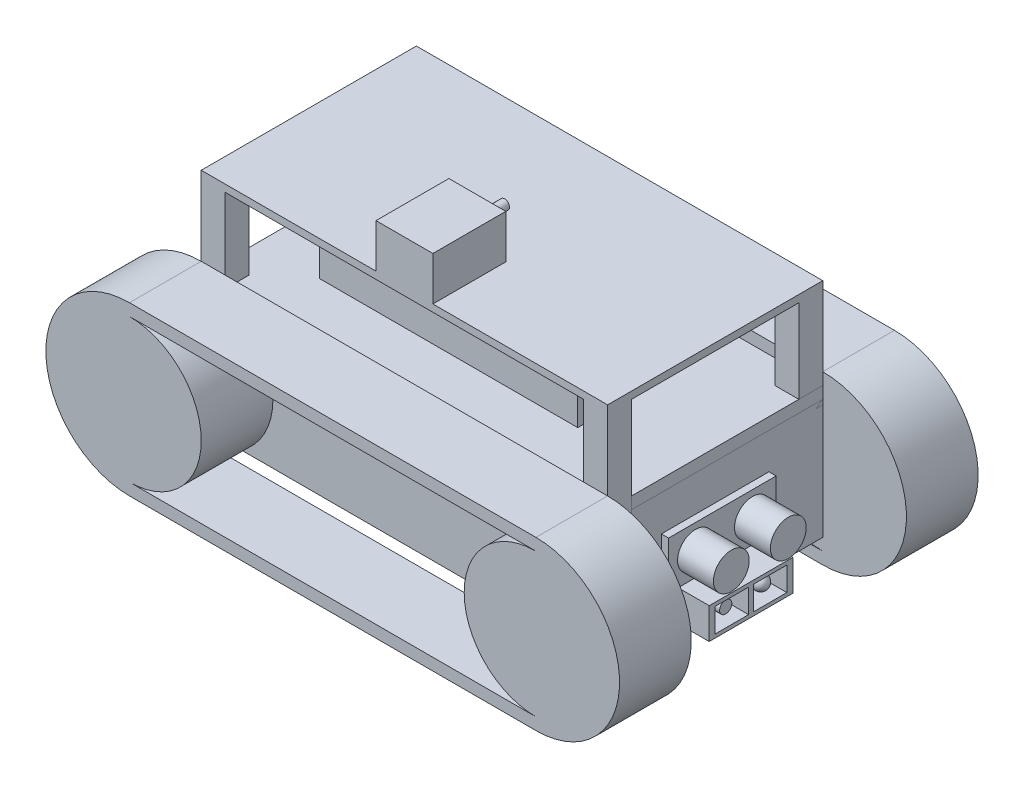
SolidWorks part; units mm, degrees
ref_plane "Front Plane" through (0, 0, 0) normal (0, 0, 1) x (1, 0, 0)
ref_plane "Top Plane" through (0, 0, 0) normal (0, 1, 0) x (1, 0, 0)
ref_plane "Right Plane" through (0, 0, 0) normal (1, 0, 0) x (0, 0, -1)
sketch "Sketch1" plane through (0, 0, 0) normal (0, 1, 0) x (1, 0, 0)
  line L1 (0, 0) -> (170, 0)
  line L2 (0, 0) -> (0, 90)
  line L3 (0, 90) -> (170, 90)
  line L4 (170, 0) -> (170, 90)
  dimension "D1" = 170
  dimension "D2" = 90
extrude "Boss-Extrude1" add sketch "Sketch1" along normal blind 50 contours L3 L4 L1 L2
sketch "Sketch2" plane through (0, 0, 0) normal (0, 0, 1) x (1, 0, 0)
  line L0 (170, 50) -> (170, 0) construction
  line L1 (0, 50) -> (0, 0) construction
  circle A0 centre (170, 25) radius 30
  circle A1 centre (0, 25) radius 30
  dimension "D1" = 60
  dimension "D2" = 60
extrude "Boss-Extrude2" add sketch "Sketch2" along normal blind 30
pattern_linear "LPattern1" count 2 spacing 120 along (0, 0, -1) of "Boss-Extrude2"
sketch "Sketch3" plane through (0, 0, 30) normal (0, 0, 1) x (1, 0, 0)
  line L0 (0, 60) -> (170, 60)
  line L1 (0, -10) -> (170, -10)
  line L2 (170, 55) -> (0, 55)
  line L3 (0, -5) -> (170, -5)
  circle A0 centre (170, 25) radius 35 construction
  circle A1 centre (0, 25) radius 35 construction
  circle A2 centre (0, 25) radius 30 construction
  circle A3 centre (170, 25) radius 30 construction
  arc A4 (170, 60) -> (170, -10) centre (170, 25) cw
  arc A5 (170, 55) -> (170, -5) centre (170, 25) cw
  arc A6 (0, 60) -> (0, -10) centre (0, 25) ccw
  arc A7 (0, -5) -> (0, 55) centre (0, 25) cw
  dimension "D1" = 70
  dimension "D2" = 70
extrude "Boss-Extrude3" add sketch "Sketch3" against normal blind 30
pattern_linear "LPattern2" count 2 spacing 120 along (0, 0, -1) of "Boss-Extrude3"
sketch "Sketch4" plane through (0, 50, 0) normal (0, 1, 0) x (1, 0, 0)
  line L1 (0, 90) -> (170, 90)
  line L2 (0, 90) -> (0, 0)
  line L3 (0, 0) -> (170, 0)
  line L4 (170, 90) -> (170, 0)
extrude "Boss-Extrude6" add sketch "Sketch4" along normal blind 5 separate body
sketch "Sketch5" plane through (0, 55, 0) normal (0, 1, 0) x (1, 0, 0)
  line L0 (85, 90) -> (85, 0)
  line L1 (170, 90) -> (0, 90) construction
  line L2 (170, 0) -> (0, 0) construction
  line L6 (31, 18.5) -> (139, 18.5) construction
  line L7 (31, 18.5) -> (31, 71.5) construction
  line L8 (31, 71.5) -> (139, 71.5) construction
  line L9 (139, 18.5) -> (139, 71.5) construction
  line L10 (31, 18.5) -> (139, 71.5)
  line L11 (31, 71.5) -> (139, 18.5)
  point P6 (85, 45)
  dimension "D1" = 53
  dimension "D2" = 108
ref_plane "Plane1" through (0, 60, 0) normal (0, 1, 0) x (1, 0, 0)
sketch "Sketch6" plane through (0, 60, 0) normal (0, 1, 0) x (1, 0, 0)
  line L1 (31, 71.5) -> (139, 71.5)
  line L2 (31, 71.5) -> (31, 18.5)
  line L3 (31, 18.5) -> (139, 18.5)
  line L4 (139, 71.5) -> (139, 18.5)
  line L5 (31, 71.5) -> (139, 18.5) construction
  line L6 (31, 18.5) -> (139, 71.5) construction
  point P0 (85, 45)
extrude "Boss-Extrude7" add sketch "Sketch6" along normal blind 15 separate body
ref_plane "Plane2" through (0, 90, 0) normal (0, 1, 0) x (1, 0, 0)
sketch "Sketch7" plane through (0, 90, 0) normal (0, 1, 0) x (1, 0, 0)
  line L0 (170, 0) -> (170, -30) construction
  line L1 (0, 90) -> (170, 90)
  line L2 (0, 90) -> (0, 0)
  line L3 (0, 0) -> (170, 0)
  line L4 (170, 90) -> (170, 0)
  line L5 (0, 90) -> (170, 0) construction
  line L6 (0, 0) -> (170, 90) construction
  line L7 (205, 0) -> (170, 0) construction
  point P0 (85, 45)
extrude "Boss-Extrude8" add sketch "Sketch7" along normal blind 3 separate body
sketch "Sketch8" plane through (0, 0, 0) normal (0, 0, 1) x (1, 0, 0)
  line L0 (85, 93) -> (85, 111.3) construction
  line L1 (0, 93) -> (170, 93) construction
  line L3 (73.1, 111.3) -> (96.9, 111.3)
  line L4 (73.1, 111.3) -> (73.1, 93)
  line L5 (73.1, 93) -> (96.9, 93)
  line L6 (96.9, 111.3) -> (96.9, 93)
  line L7 (73.1, 111.3) -> (96.9, 93) construction
  line L8 (73.1, 93) -> (96.9, 111.3) construction
  point P4 (85, 102.15)
  dimension "D1" = 18.3
  dimension "D2" = 23.8
extrude "Boss-Extrude9" add sketch "Sketch8" against normal blind 30.5
sketch "Sketch9" plane through (0, 0, -30.5) normal (0, 0, -1) x (-1, 0, 0)
  line L0 (-85, 111.3) -> (-85, 93) construction
  line L1 (-96.9, 111.3) -> (-73.1, 111.3) construction
  line L2 (-73.1, 93) -> (-96.9, 93) construction
  circle A0 centre (-85, 102.15) radius 2.0061
extrude "Boss-Extrude10" add sketch "Sketch9" along normal blind 11.45
sketch "Sketch10" plane through (170, 0, 0) normal (1, 0, 0) x (0, 0, -1)
  line L0 (45, 50) -> (45, 0) construction
  line L1 (0, 50) -> (90, 50) construction
  line L2 (0, 0) -> (90, 0) construction
  line L4 (22.5, 35) -> (67.5, 35)
  line L5 (22.5, 35) -> (22.5, 15)
  line L6 (22.5, 15) -> (67.5, 15)
  line L7 (67.5, 35) -> (67.5, 15)
  line L8 (22.5, 35) -> (67.5, 15) construction
  line L9 (22.5, 15) -> (67.5, 35) construction
  point P6 (45, 25)
  dimension "D1" = 20
  dimension "D2" = 45
extrude "Boss-Extrude11" add sketch "Sketch10" along normal blind 3
sketch "Sketch11" plane through (173, 0, 0) normal (1, 0, 0) x (0, 0, -1)
  line L0 (45, 35) -> (45, 15) construction
  line L1 (67.5, 35) -> (22.5, 35) construction
  line L2 (22.5, 15) -> (67.5, 15) construction
  line L3 (45, 25) -> (22.5, 25) construction
  line L4 (22.5, 35) -> (22.5, 15) construction
  line L5 (45, 25) -> (67.5, 25) construction
  line L6 (67.5, 15) -> (67.5, 35) construction
  circle A0 centre (57.5882, 25) radius 7.5
  circle A1 centre (33.75, 25) radius 7.5
  dimension "D1" = 15
  dimension "D2" = 15
extrude "Boss-Extrude12" add sketch "Sketch11" along normal blind 15
sketch "Sketch12" plane through (170, 0, 0) normal (1, 0, 0) x (0, 0, -1)
  line L0 (45, 15) -> (45, 0) construction
  line L1 (22.5, 15) -> (67.5, 15) construction
  line L2 (0, 0) -> (90, 0) construction
  line L3 (30, 12.5) -> (44, 12.5)
  line L4 (30, 12.5) -> (60, 12.5) construction
  line L5 (30, 12.5) -> (30, 2.5)
  line L6 (30, 2.5) -> (60, 2.5) construction
  line L7 (60, 12.5) -> (60, 2.5)
  line L8 (30, 12.5) -> (60, 2.5) construction
  line L9 (30, 2.5) -> (60, 12.5) construction
  line L10 (27.5, 14) -> (62.5, 14)
  line L11 (27.5, 14) -> (27.5, 1)
  line L12 (27.5, 1) -> (62.5, 1)
  line L13 (62.5, 14) -> (62.5, 1)
  line L14 (27.5, 14) -> (62.5, 1) construction
  line L15 (27.5, 1) -> (62.5, 14) construction
  line L16 (44, 12.5) -> (46, 12.5) construction
  line L17 (44, 12.5) -> (44, 2.5)
  line L18 (44, 2.5) -> (46, 2.5) construction
  line L19 (46, 12.5) -> (46, 2.5)
  line L20 (44, 12.5) -> (46, 2.5) construction
  line L21 (44, 2.5) -> (46, 12.5) construction
  line L22 (60, 12.5) -> (46, 12.5)
  line L23 (46, 2.5) -> (60, 2.5)
  line L24 (30, 2.5) -> (44, 2.5)
  point P6 (45, 7.5)
  point P11 (45, 7.5)
  point P16 (45, 7.5)
  dimension "D1" = 30
  dimension "D2" = 10
  dimension "D3" = 35
  dimension "D4" = 13
  dimension "D5" = 2
extrude "Boss-Extrude13" add sketch "Sketch12" along normal blind 15
ref_plane "Plane3" through (180, 0, 0) normal (1, 0, 0) x (0, 0, -1)
sketch "Sketch13" plane through (180, 0, 0) normal (1, 0, 0) x (0, 0, -1)
  line L0 (37, 12.5) -> (37, 2.5) construction
  line L1 (44, 12.5) -> (30, 12.5) construction
  line L2 (30, 2.5) -> (44, 2.5) construction
  circle A0 centre (37, 7.5) radius 2.55
  dimension "D1" = 5.1
extrude "Boss-Extrude14" add sketch "Sketch13" along normal blind 2.4 separate body
ref_plane "Plane4" through (175.4, 0, 0) normal (1, 0, 0) x (0, 0, -1)
sketch "Sketch14" plane through (175.4, 0, 0) normal (1, 0, 0) x (0, 0, -1)
  line L0 (53, 12.5) -> (53, 2.5) construction
  line L1 (60, 12.5) -> (46, 12.5) construction
  line L2 (46, 2.5) -> (60, 2.5) construction
  circle A0 centre (53, 7.8643) radius 3
  dimension "D1" = 6
extrude "Boss-Extrude15" add sketch "Sketch14" along normal blind 8.6 separate body contours A0
fillet "Fillet1" radius 3 1 edges at (184, 7.8643, -56)
sketch "Sketch15" plane through (0, 0, 0) normal (-1, 0, 0) x (0, 0, 1)
  line L0 (-45, 0) -> (-45, 15) construction
  line L1 (0, 0) -> (-90, 0) construction
  line L3 (-62.5, 15) -> (-27.5, 15)
  line L4 (-62.5, 15) -> (-62.5, 0)
  line L5 (-62.5, 0) -> (-27.5, 0)
  line L6 (-27.5, 15) -> (-27.5, 0)
  line L7 (-62.5, 15) -> (-27.5, 0) construction
  line L8 (-62.5, 0) -> (-27.5, 15) construction
  point P4 (-45, 7.5)
  dimension "D1" = 15
  dimension "D2" = 35
extrude "Boss-Extrude16" add sketch "Sketch15" along normal blind 13
sketch "Sketch17" plane through (0, 0, 0) normal (0, -1, 0) x (1, 0, 0)
  line L0 (0, -62.5) -> (0, -90) construction
  line L1 (-13, -27.5) -> (0, -27.5) construction
  line L2 (-13, -27.5) -> (-13, -62.5) construction
  line L3 (-13, -62.5) -> (0, -62.5) construction
  line L4 (0, -27.5) -> (0, -62.5) construction
  line L5 (0, -45) -> (-13, -45) construction
  line L7 (-11.5, -60) -> (-1.5, -60)
  line L8 (-11.5, -60) -> (-11.5, -30)
  line L9 (-11.5, -30) -> (-1.5, -30)
  line L10 (-1.5, -60) -> (-1.5, -30)
  line L11 (-11.5, -60) -> (-1.5, -30) construction
  line L12 (-11.5, -30) -> (-1.5, -60) construction
  point P9 (-6.5, -45)
  dimension "D1" = 30
  dimension "D2" = 10
extrude "Cut-Extrude1" cut sketch "Sketch17" against normal blind 12 contours L8 L9 L10 L7
sketch "Sketch18" plane through (0, 12, 0) normal (0, -1, 0) x (1, 0, 0)
  line L0 (-11.5, -44.4175) -> (-1.5, -44.4175) construction
  line L1 (-11.5, -60) -> (-11.5, -30) construction
  line L2 (-1.5, -60) -> (-1.5, -30) construction
  line L4 (-11.5, -43.4175) -> (-1.5, -43.4175)
  line L5 (-11.5, -43.4175) -> (-11.5, -45.4175)
  line L6 (-11.5, -45.4175) -> (-1.5, -45.4175)
  line L7 (-1.5, -43.4175) -> (-1.5, -45.4175)
  line L8 (-11.5, -43.4175) -> (-1.5, -45.4175) construction
  line L9 (-11.5, -45.4175) -> (-1.5, -43.4175) construction
  point P6 (-6.5, -44.4175)
  dimension "D1" = 2
extrude "Boss-Extrude17" add sketch "Sketch18" along normal blind 12
sketch "Sketch20" plane through (0, 90, 0) normal (0, -1, 0) x (1, 0, 0)
  line L1 (0, 0) -> (10, 0)
  line L2 (0, 0) -> (0, -10)
  line L3 (0, -10) -> (10, -10)
  line L4 (10, 0) -> (10, -10)
  line L5 (170, 0) -> (170, -90) construction
  line L6 (170, 0) -> (160, 0)
  line L7 (170, 0) -> (170, -10)
  line L8 (170, -10) -> (160, -10)
  line L11 (160, 0) -> (160, -10)
  line L12 (0, 0) -> (170, 0) construction
  line L13 (170, -90) -> (0, -90) construction
  line L14 (170, -90) -> (160, -90)
  line L16 (170, -90) -> (170, -80)
  line L17 (170, -80) -> (160, -80)
  line L18 (160, -90) -> (160, -80)
  line L19 (0, -90) -> (0, 0) construction
  line L20 (0, -90) -> (10, -90)
  line L21 (0, -90) -> (0, -80)
  line L22 (0, -80) -> (10, -80)
  line L23 (10, -90) -> (10, -80)
  dimension "D1" = 10
  dimension "D2" = 10
  dimension "D3" = 10
  dimension "D4" = 10
extrude "Boss-Extrude20" add sketch "Sketch20" along normal blind 42
